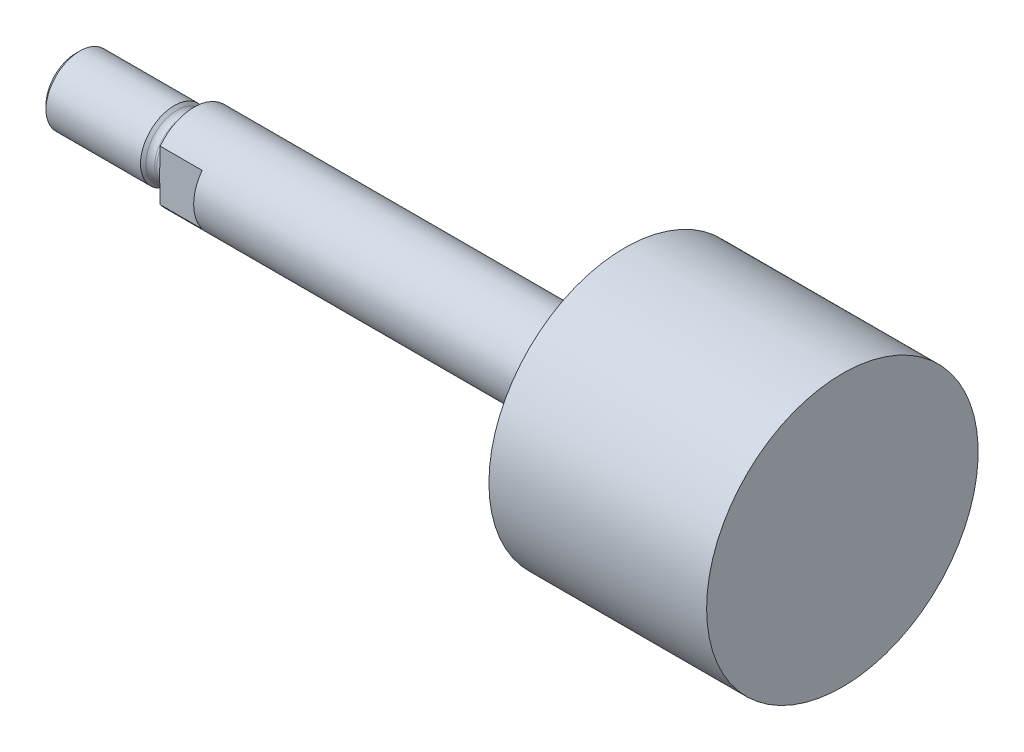
SolidWorks part; units mm, degrees
material "Cast Alloy Steel"
ref_plane "Front Plane" through (0, 0, 0) normal (0, 0, 1) x (1, 0, 0)
ref_plane "Top Plane" through (0, 0, 0) normal (0, 1, 0) x (1, 0, 0)
ref_plane "Right Plane" through (0, 0, 0) normal (1, 0, 0) x (0, 0, -1)
sketch "Sketch1" plane through (0, 0, 0) normal (0, 0, 1) x (1, 0, 0)
  line L0 (-9.525, 0) -> (-9.525, 7.9375)
  line L1 (-9.525, 7.9375) -> (71.4248, 7.9375)
  line L2 (71.4248, 7.9375) -> (71.4248, 25.5206)
  line L3 (71.4248, 25.5206) -> (112.3442, 25.5206)
  line L4 (112.3442, 25.5206) -> (112.3442, 0)
  line L5 (112.3442, 0) -> (-9.525, 0)
  line L6 (112.3442, 0) -> (-9.525, 0) construction
revolve "Revolve1" add sketch "Sketch1" angle 360 about L6 reverse direction yes
sketch "Sketch2" plane through (0, 0, 0) normal (0, 0, 1) x (1, 0, 0)
  line L0 (-31.75, 0) -> (-31.75, 5.5944)
  line L1 (-31.75, 5.5944) -> (-30.9944, 6.35)
  line L2 (-30.9944, 6.35) -> (-13.2334, 6.35)
  line L3 (-13.2334, 6.35) -> (-12.7264, 5.843)
  line L4 (-11.5589, 5.3594) -> (-11.176, 5.3594)
  line L5 (-9.525, 7.0104) -> (-9.525, 0)
  line L6 (-9.525, 0) -> (-31.75, 0)
  line L7 (-9.525, 0) -> (-31.75, 0) construction
  arc A0 (-12.7264, 5.843) -> (-11.5589, 5.3594) centre (-11.5589, 7.0104) ccw
  arc A1 (-11.176, 5.3594) -> (-9.525, 7.0104) centre (-11.176, 7.0104) ccw
revolve "Revolve2" add sketch "Sketch2" angle 360 about L7 reverse direction yes
cosmetic thread "Cosmetic Thread1" parameters "D1"=18.5166, "D2"=11.1887
ref_plane "Plane1" through (0, 0, 0) normal (1, 0, 0) x (0, 0, -1)
ref_plane "Plane2" through (-9.525, 0, 0) normal (1, 0, 0) x (0, 0, -1)
ref_plane "Plane3" through (-10.16, 0, 0) normal (1, 0, 0) x (0, 0, -1)
sketch "Sketch3" plane through (-10.16, 0, 0) normal (1, 0, 0) x (0, 0, -1)
  line L0 (-15.875, 15.875) -> (-15.875, -15.875)
  line L1 (-15.875, -15.875) -> (15.875, -15.875)
  line L2 (15.875, -15.875) -> (15.875, 15.875)
  line L3 (15.875, 15.875) -> (-15.875, 15.875)
  line L4 (-6.35, 7.9375) -> (-6.35, -7.9375)
  line L5 (-6.35, -7.9375) -> (6.35, -7.9375)
  line L6 (6.35, -7.9375) -> (6.35, 7.9375)
  line L7 (6.35, 7.9375) -> (-6.35, 7.9375)
extrude "Cut-Extrude1" cut sketch "Sketch3" along normal blind 8.509
ref_plane "Plane4" through (193.294, 0, 0) normal (1, 0, 0) x (0, 0, -1)
ref_plane "Plane5" through (-31.75, 0, 0) normal (1, 0, 0) x (0, 0, -1)
ref_plane "Plane6" through (-9.525, 0, 0) normal (1, 0, 0) x (0, 0, -1)
ref_plane "Plane7" through (-9.525, 0, 0) normal (1, 0, 0) x (0, 0, -1)
ref_plane "Plane8" through (-1.651, 0, 0) normal (1, 0, 0) x (0, 0, -1)
ref_plane "Plane9" through (0, 0, 0) normal (1, 0, 0) x (0, 0, -1)
ref_plane "Plane10" through (0, 0, 0) normal (0, 1, 0) x (1, 0, 0)
ref_plane "Plane11" through (-36.449, 0, 0) normal (1, 0, 0) x (0, 0, -1)
ref_plane "dia1 XY" through (-9.525, 0, 0) normal (1, 0, 0) x (0, 0, -1)
ref_plane "dia1 XZ" through (0, 7.9375, 0) normal (0, -1, 0) x (-1, 0, 0)
ref_plane "dia1 YZ" through (0, 0, 0) normal (0, 0, -1) x (-1, 0, 0)
ref_axis "dia1 X" through (-9.525, 7.9375, 80.9) along (0, 0, -1)
ref_axis "dia1 Y" through (-9.525, -50, 0) along (0, 1, 0)
ref_axis "dia1 Z" through (80.9, 7.9375, 0) along (-1, 0, 0)
sketch3d "dia1"
  point P0 (-9.525, 7.9375, 0)
ref_plane "dia12 XY" through (0, 0, 0) normal (1, 0, 0) x (0, 0, -1)
ref_plane "dia12 XZ" through (0, 0, 0) normal (0, -1, 0) x (-1, 0, 0)
ref_plane "dia12 YZ" through (0, 0, 26.4858) normal (0, 0, -1) x (-1, 0, 0)
ref_axis "dia12 X" through (0, 0, 80.9) along (0, 0, -1)
ref_axis "dia12 Y" through (0, -50, 26.4858) along (0, 1, 0)
ref_axis "dia12 Z" through (80.9, 0, 26.4858) along (-1, 0, 0)
sketch3d "dia12"
  point P0 (0, 0, 26.4858)
ref_plane "dia2 XY" through (-9.525, 0, 0) normal (1, 0, 0) x (0, 0, -1)
ref_plane "dia2 XZ" through (0, -7.9375, 0) normal (0, -1, 0) x (-1, 0, 0)
ref_plane "dia2 YZ" through (0, 0, 0) normal (0, 0, -1) x (-1, 0, 0)
ref_axis "dia2 X" through (-9.525, -7.9375, 80.9) along (0, 0, -1)
ref_axis "dia2 Y" through (-9.525, -50, 0) along (0, 1, 0)
ref_axis "dia2 Z" through (80.9, -7.9375, 0) along (-1, 0, 0)
sketch3d "dia2"
  point P0 (-9.525, -7.9375, 0)
ref_plane "dia22 XY" through (0, 0, 0) normal (1, 0, 0) x (0, 0, -1)
ref_plane "dia22 XZ" through (0, 0, 0) normal (0, -1, 0) x (-1, 0, 0)
ref_plane "dia22 YZ" through (0, 0, -26.4858) normal (0, 0, -1) x (-1, 0, 0)
ref_axis "dia22 X" through (0, 0, 80.9) along (0, 0, -1)
ref_axis "dia22 Y" through (0, -50, -26.4858) along (0, 1, 0)
ref_axis "dia22 Z" through (80.9, 0, -26.4858) along (-1, 0, 0)
sketch3d "dia22"
  point P0 (0, 0, -26.4858)
ref_plane "rl1 XY" through (-31.75, 0, 0) normal (1, 0, 0) x (0, 0, -1)
ref_plane "rl1 XZ" through (0, 0, 0) normal (0, -1, 0) x (-1, 0, 0)
ref_plane "rl1 YZ" through (0, 0, 0) normal (0, 0, -1) x (-1, 0, 0)
ref_axis "rl1 X" through (-31.75, 0, 80.9) along (0, 0, -1)
ref_axis "rl1 Y" through (-31.75, -50, 0) along (0, 1, 0)
ref_axis "rl1 Z" through (80.9, 0, 0) along (-1, 0, 0)
sketch3d "rl1"
  point P0 (-31.75, 0, 0)
ref_plane "rl2 XY" through (-9.525, 0, 0) normal (1, 0, 0) x (0, 0, -1)
ref_plane "rl2 XZ" through (0, 0, 0) normal (0, -1, 0) x (-1, 0, 0)
ref_plane "rl2 YZ" through (0, 0, 0) normal (0, 0, -1) x (-1, 0, 0)
ref_axis "rl2 X" through (-9.525, 0, 80.9) along (0, 0, -1)
ref_axis "rl2 Y" through (-9.525, -50, 0) along (0, 1, 0)
ref_axis "rl2 Z" through (80.9, 0, 0) along (-1, 0, 0)
sketch3d "rl2"
  point P0 (-9.525, 0, 0)
ref_plane "rod_cp XY" through (0, 0, 0) normal (1, 0, 0) x (0, 0, -1)
ref_plane "rod_cp XZ" through (0, 0, 0) normal (0, -1, 0) x (-1, 0, 0)
ref_plane "rod_cp YZ" through (0, 0, 0) normal (0, 0, -1) x (-1, 0, 0)
ref_axis "rod_cp X" through (0, 0, 80.9) along (0, 0, -1)
ref_axis "rod_cp Y" through (0, -50, 0) along (0, 1, 0)
ref_axis "rod_cp Z" through (80.9, 0, 0) along (-1, 0, 0)
sketch3d "rod_cp"
  point P0 (0, 0, 0)
ref_plane "stroke1 XY" through (-9.525, 0, 0) normal (1, 0, 0) x (0, 0, -1)
ref_plane "stroke1 XZ" through (0, 0, 0) normal (0, -1, 0) x (-1, 0, 0)
ref_plane "stroke1 YZ" through (0, 0, 0) normal (0, 0, -1) x (-1, 0, 0)
ref_axis "stroke1 X" through (-9.525, 0, 80.9) along (0, 0, -1)
ref_axis "stroke1 Y" through (-9.525, -50, 0) along (0, 1, 0)
ref_axis "stroke1 Z" through (80.9, 0, 0) along (-1, 0, 0)
sketch3d "stroke1"
  point P0 (-9.525, 0, 0)
ref_plane "thd1 XY" through (-31.75, 0, 0) normal (1, 0, 0) x (0, 0, -1)
ref_plane "thd1 XZ" through (0, 6.35, 0) normal (0, -1, 0) x (-1, 0, 0)
ref_plane "thd1 YZ" through (0, 0, 0) normal (0, 0, -1) x (-1, 0, 0)
ref_axis "thd1 X" through (-31.75, 6.35, 80.9) along (0, 0, -1)
ref_axis "thd1 Y" through (-31.75, -50, 0) along (0, 1, 0)
ref_axis "thd1 Z" through (80.9, 6.35, 0) along (-1, 0, 0)
sketch3d "thd1"
  point P0 (-31.75, 6.35, 0)
ref_plane "thd2 XY" through (-31.75, 0, 0) normal (1, 0, 0) x (0, 0, -1)
ref_plane "thd2 XZ" through (0, -6.35, 0) normal (0, -1, 0) x (-1, 0, 0)
ref_plane "thd2 YZ" through (0, 0, 0) normal (0, 0, -1) x (-1, 0, 0)
ref_axis "thd2 X" through (-31.75, -6.35, 80.9) along (0, 0, -1)
ref_axis "thd2 Y" through (-31.75, -50, 0) along (0, 1, 0)
ref_axis "thd2 Z" through (80.9, -6.35, 0) along (-1, 0, 0)
sketch3d "thd2"
  point P0 (-31.75, -6.35, 0)
ref_plane "to_rod_clevis XY" through (-36.449, 0, 0) normal (1, 0, 0) x (0, 0, -1)
ref_plane "to_rod_clevis XZ" through (0, 0, 0) normal (0, -1, 0) x (-1, 0, 0)
ref_plane "to_rod_clevis YZ" through (0, 0, 0) normal (0, 0, -1) x (-1, 0, 0)
ref_axis "to_rod_clevis X" through (-36.449, 0, 80.9) along (0, 0, -1)
ref_axis "to_rod_clevis Y" through (-36.449, -50, 0) along (0, 1, 0)
ref_axis "to_rod_clevis Z" through (80.9, 0, 0) along (-1, 0, 0)
sketch3d "to_rod_clevis"
  point P0 (-36.449, 0, 0)
ref_plane "wf1 XY" through (-9.525, 0, 0) normal (1, 0, 0) x (0, 0, -1)
ref_plane "wf1 XZ" through (0, 0, 0) normal (0, -1, 0) x (-1, 0, 0)
ref_plane "wf1 YZ" through (0, 0, 0) normal (0, 0, -1) x (-1, 0, 0)
ref_axis "wf1 X" through (-9.525, 0, 80.9) along (0, 0, -1)
ref_axis "wf1 Y" through (-9.525, -50, 0) along (0, 1, 0)
ref_axis "wf1 Z" through (80.9, 0, 0) along (-1, 0, 0)
sketch3d "wf1"
  point P0 (-9.525, 0, 0)
ref_plane "wf2 XY" through (-1.651, 0, 0) normal (1, 0, 0) x (0, 0, -1)
ref_plane "wf2 XZ" through (0, 0, 0) normal (0, -1, 0) x (-1, 0, 0)
ref_plane "wf2 YZ" through (0, 0, 0) normal (0, 0, -1) x (-1, 0, 0)
ref_axis "wf2 X" through (-1.651, 0, 80.9) along (0, 0, -1)
ref_axis "wf2 Y" through (-1.651, -50, 0) along (0, 1, 0)
ref_axis "wf2 Z" through (80.9, 0, 0) along (-1, 0, 0)
sketch3d "wf2"
  point P0 (-1.651, 0, 0)
ref_plane "wfw1 XY" through (0, 0, 0) normal (0, 1, 0) x (1, 0, 0)
ref_plane "wfw1 XZ" through (0, 0, -6.35) normal (0, 0, 1) x (1, 0, 0)
ref_plane "wfw1 YZ" through (-9.525, 0, 0) normal (1, 0, 0) x (0, 0, -1)
ref_axis "wfw1 X" through (-80.9, 0, -6.35) along (1, 0, 0)
ref_axis "wfw1 Y" through (-9.525, 0, 50) along (0, 0, -1)
ref_axis "wfw1 Z" through (-9.525, 50, -6.35) along (0, -1, 0)
sketch3d "wfw1"
  point P0 (-9.525, 0, -6.35)
ref_plane "wfw2 XY" through (0, 0, 0) normal (0, 1, 0) x (1, 0, 0)
ref_plane "wfw2 XZ" through (0, 0, 6.35) normal (0, 0, 1) x (1, 0, 0)
ref_plane "wfw2 YZ" through (-9.525, 0, 0) normal (1, 0, 0) x (0, 0, -1)
ref_axis "wfw2 X" through (-80.9, 0, 6.35) along (1, 0, 0)
ref_axis "wfw2 Y" through (-9.525, 0, 50) along (0, 0, -1)
ref_axis "wfw2 Z" through (-9.525, 50, 6.35) along (0, -1, 0)
sketch3d "wfw2"
  point P0 (-9.525, 0, 6.35)
